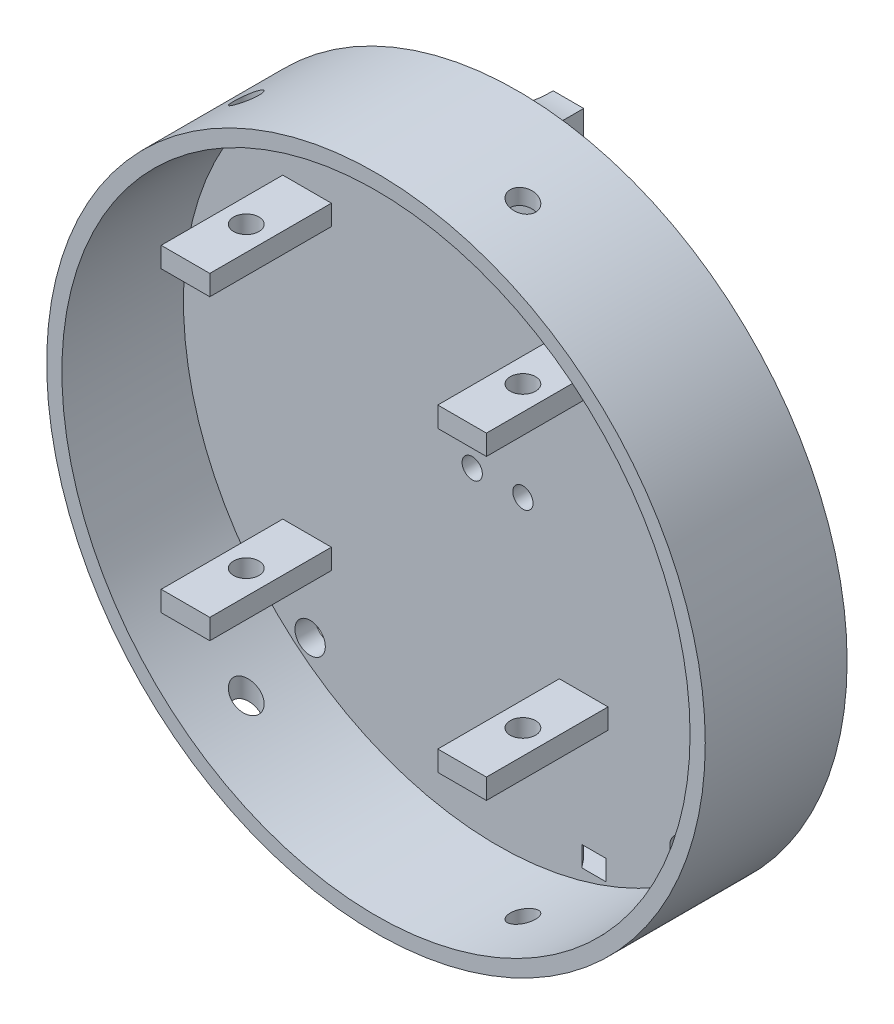
SolidWorks part; units mm, degrees
ref_plane "Alzado" through (0, 0, 0) normal (0, 0, 1) x (1, 0, 0)
ref_plane "Planta" through (0, 0, 0) normal (0, 1, 0) x (1, 0, 0)
ref_plane "Vista lateral" through (0, 0, 0) normal (1, 0, 0) x (0, 0, -1)
sketch "Croquis1" plane through (0, 0, 0) normal (0, 0, 1) x (1, 0, 0)
  line L0 (10, 20) -> (-10, 20) construction
  circle A0 centre (0, 0) radius 32.5
  circle A1 centre (-2.5, 0) radius 1
  circle A2 centre (2.5, 0) radius 1
  circle A3 centre (0, 20) radius 1
  circle A4 centre (10, 20) radius 1
  circle A5 centre (-10, 20) radius 1
  point P9 (0, 20)
  dimension "D1" = 65
  dimension "D4" = 2
  dimension "D7" = 2
  dimension "D2" = 2.5
  dimension "D3" = 2.5
  dimension "D5" = 20
  dimension "D6" = 20
extrude "Saliente-Extruir1" add sketch "Croquis1" along normal blind 2
sketch "Croquis2" plane through (0, 0, 2) normal (0, 0, 1) x (1, 0, 0)
  line L0 (-21.2, -15.7) -> (-16.4, -15.7)
  line L1 (10.9, -15.7) -> (6.1, -15.7)
  line L2 (-21.2, -15.7) -> (-21.2, -13.7)
  line L3 (-21.2, -13.7) -> (-16.4, -13.7)
  line L4 (-16.4, -13.7) -> (-16.4, -15.7)
  line L5 (6.1, -15.7) -> (6.1, -13.7)
  line L6 (6.1, -13.7) -> (10.9, -13.7)
  line L7 (10.9, -13.7) -> (10.9, -15.7)
  line L8 (6.1, -15.7) -> (10.9, -15.7)
  line L9 (0, 0) -> (12.8027, 0) construction
  line L10 (10.9, 13.7) -> (10.9, 15.7)
  line L11 (10.9, 15.7) -> (6.1, 15.7)
  line L12 (6.1, 13.7) -> (10.9, 13.7)
  line L13 (6.1, 15.7) -> (6.1, 13.7)
  line L14 (-16.4, 13.7) -> (-16.4, 15.7)
  line L15 (-21.2, 15.7) -> (-16.4, 15.7)
  line L16 (-21.2, 15.7) -> (-21.2, 13.7)
  line L17 (-21.2, 13.7) -> (-16.4, 13.7)
  point P2 (0, -15.7)
  point P3 (-16.4, -15.7)
  point P13 (8.5, -15.7)
  point P16 (8.5, 15.7)
  dimension "D1" = 32.1
  dimension "D2" = 10.9
  dimension "D3" = 15.7
  dimension "D4" = 4.8
  dimension "D5" = 4.8
  dimension "D6" = 2
  dimension "D7" = 2
extrude "Saliente-Extruir2" add sketch "Croquis2" along normal blind 12 contours L7 L6 L5 L1 | L4 L3 L2 L0 | L16 L17 L14 L15 | L11 L13 L12 L10 region at (-18.8, -14.7, 2) region at (8.5, -14.7, 2) region at (8.5, 14.7, 2) region at (-18.8, 14.7, 2)
sketch "Croquis3" plane through (0, -15.7, 0) normal (0, -1, 0) x (1, 0, 0)
  line L0 (-18.8, 14) -> (-18.8, 2) construction
  line L1 (-21.2, 14) -> (-16.4, 14) construction
  line L2 (-21.2, 2) -> (-16.4, 2) construction
  line L3 (8.5, 14) -> (8.5, 2) construction
  line L4 (10.9, 14) -> (6.1, 14) construction
  line L5 (10.9, 2) -> (6.1, 2) construction
  circle A0 centre (-18.8, 8) radius 1.25
  circle A1 centre (8.5, 8) radius 1.25
  dimension "D1" = 2.5
extrude "Cortar-Extruir1" cut sketch "Croquis3" against normal up to surface (31.4 mm away) up to face at (8.5, 15.7, 8)
ref_plane "Plano1" through (0, -32.5, 0) normal (0, -1, 0) x (-1, 0, 0)
ref_plane "Plano2" through (0, -28.75, 0) normal (0, -1, 0) x (-1, 0, 0)
sketch "Croquis5" plane through (0, -28.75, 0) normal (0, -1, 0) x (-1, 0, 0)
  line L0 (-8.5, -8) -> (18.8, -8) construction
  line L1 (0, 0) -> (0, -8) construction
  line L2 (-32.5, -2) -> (32.5, -2) construction
  line L3 (-10.68, -2) -> (-8.3104, -2)
  line L4 (32.5, 0) -> (-32.5, 0) construction
  line L5 (9.277, 0) -> (6.408, 0)
  line L6 (8.3104, -2) -> (10.68, -2)
  line L7 (-6.408, 0) -> (-9.277, 0)
  arc A0 (-9.277, 0) -> (-10.68, -2) centre (0, -8) ccw
  arc A1 (-6.408, 0) -> (-8.3104, -2) centre (0, -8) ccw
  arc A2 (10.68, -2) -> (9.277, 0) centre (0, -8) ccw
  arc A3 (8.3104, -2) -> (6.408, 0) centre (0, -8) ccw
  dimension "D1" = 24.5
  dimension "D2" = 20.5
extrude "Cortar-Extruir3" cut sketch "Croquis5" against normal blind 2
mirror "Simetría1" about plane through (0, 0, 0) normal (0, 1, 0) of "Cortar-Extruir3"
sketch "Croquis6" plane through (0, 0, 0) normal (0, 0, -1) x (-1, 0, 0)
  line L1 (-18.5, 22.5) -> (18.5, 22.5) construction
  line L2 (-18.5, 22.5) -> (-18.5, -22.5) construction
  line L3 (-18.5, -22.5) -> (18.5, -22.5) construction
  line L4 (18.5, 22.5) -> (18.5, -22.5) construction
  line L5 (-18.5, 22.5) -> (18.5, -22.5) construction
  line L6 (-18.5, -22.5) -> (18.5, 22.5) construction
  circle A0 centre (-18.5, 22.5) radius 1.5
  circle A1 centre (18.5, 22.5) radius 1.5
  circle A2 centre (18.5, -22.5) radius 1.5
  circle A3 centre (-18.5, -22.5) radius 1.5
  point P0 (0, 0)
  dimension "D3" = 3
  dimension "D1" = 45
  dimension "D2" = 37
extrude "Cortar-Extruir4" cut sketch "Croquis6" against normal blind 2.5
sketch "Croquis7" plane through (0, 0, 2) normal (0, 0, 1) x (1, 0, 0)
  circle A2 centre (0, 0) radius 32.5 construction
  circle A9 centre (0, 0) radius 32.5
  circle A11 centre (0, 0) radius 31
  dimension "D1" = 1.5
extrude "Saliente-Extruir3" add sketch "Croquis7" along normal blind 12
ref_plane "Plano3" through (0, -32.5, 0) normal (0, -1, 0) x (-1, 0, 0)
sketch "Croquis8" plane through (0, -32.5, 0) normal (0, -1, 0) x (-1, 0, 0)
  circle A0 centre (-8.5, -8) radius 1.25 construction
  circle A1 centre (-8.5, -8) radius 1.25
  circle A2 centre (18.8, -8) radius 1.25 construction
  circle A3 centre (18.8, -8) radius 1.25
extrude "Cortar-Extruir5" cut sketch "Croquis8" against normal blind 70
sketch "Sketch1" plane through (0, 0, 0) normal (0, 0, -1) x (-1, 0, 0)
  line L0 (6.408, 26.75) -> (6.408, 28.75) construction
  line L1 (-1.502, 29.25) -> (1.498, 29.25)
  line L2 (-1.502, 29.25) -> (-1.502, 26.25)
  line L3 (-1.502, 26.25) -> (1.498, 26.25)
  line L4 (1.498, 29.25) -> (1.498, 26.25)
  line L5 (-1.502, 29.25) -> (1.498, 26.25) construction
  line L6 (-1.502, 26.25) -> (1.498, 29.25) construction
  line L7 (0, 0) -> (-11.4103, 0) construction
  line L8 (-1.502, -26.25) -> (1.498, -29.25) construction
  line L9 (-1.502, -29.25) -> (1.498, -26.25) construction
  line L10 (1.498, -29.25) -> (1.498, -26.25)
  line L11 (-1.502, -26.25) -> (1.498, -26.25)
  line L12 (-1.502, -29.25) -> (-1.502, -26.25)
  line L13 (-1.502, -29.25) -> (1.498, -29.25)
  line L14 (-6.408, -26.75) -> (-6.408, -28.75) construction
  point P0 (-0.002, 27.75)
  point P8 (6.408, 27.75)
  point P15 (-0.002, -27.75)
  dimension "D1" = 4.91
  dimension "D2" = 3
  dimension "D3" = 3
  dimension "D4" = 4.906
extrude "Boss-Extrude1" add sketch "Sketch1" along normal blind 5
fillet "Fillet1" radius 2 6 edges at (1.502, 27.75, 0) (-1.498, -27.75, 0) (0.002, 26.25, 0) (0.002, 29.25, 0) (0.002, -26.25, 0) (0.002, -29.25, 0) second distance 5 first distance on face at (0.002, 27.75, 0)
sketch "Sketch2" plane through (0, 0, 2) normal (0, 0, 1) x (1, 0, 0)
  line L1 (-10.68, -26.75) -> (-5.6668, -26.75)
  line L2 (-10.68, -26.75) -> (-10.68, -28.75)
  line L3 (-10.68, -28.75) -> (-5.6668, -28.75)
  line L4 (-5.6668, -26.75) -> (-5.6668, -28.75)
  line L5 (10.68, 26.75) -> (5.4941, 26.75)
  line L6 (10.68, 26.75) -> (10.68, 28.75)
  line L7 (10.68, 28.75) -> (5.4941, 28.75)
  line L8 (5.4941, 26.75) -> (5.4941, 28.75)
extrude "Tapon" add sketch "Sketch2" against normal up to surface (2 mm away) up to face at (1.002, 26, 0)
